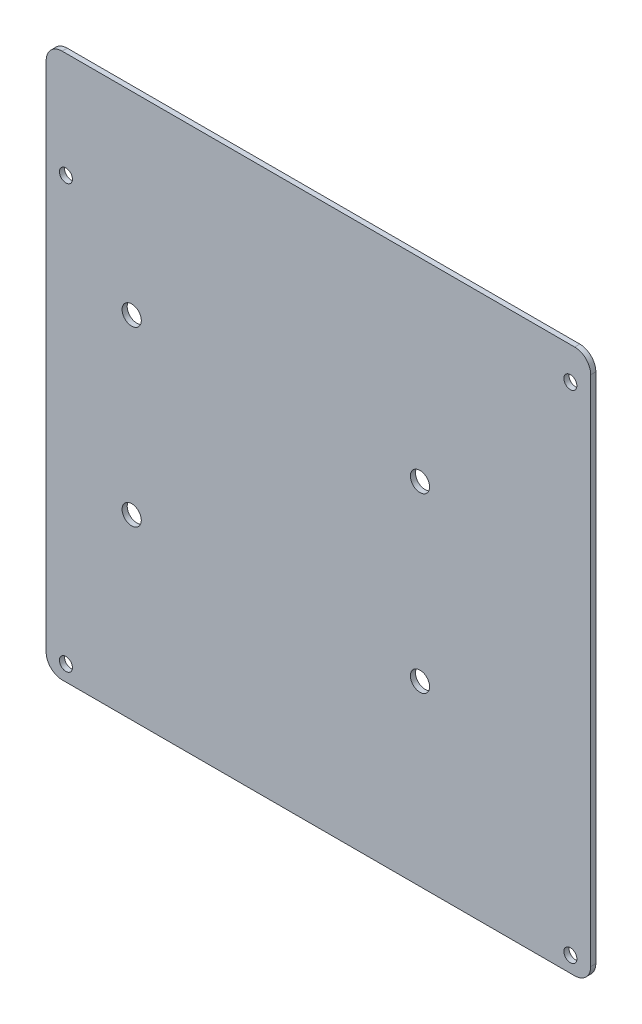
SolidWorks part; units mm, degrees
material "Epoxy, Unfilled"
ref_plane "Front Plane" through (0, 0, 0) normal (0, 0, 1) x (1, 0, 0)
ref_plane "Top Plane" through (0, 0, 0) normal (0, 1, 0) x (1, 0, 0)
ref_plane "Right Plane" through (0, 0, 0) normal (1, 0, 0) x (0, 0, -1)
sketch "Sketch1" plane through (0, 0, 0) normal (0, 0, 1) x (1, 0, 0)
  line L1 (85, -85) -> (-85, -85)
  line L2 (85, -85) -> (85, 85)
  line L3 (85, 85) -> (-85, 85)
  line L4 (-85, -85) -> (-85, 85)
  line L5 (85, -85) -> (-85, 85) construction
  line L6 (85, 85) -> (-85, -85) construction
  point P0 (0, 0)
  dimension "D1" = 170
  dimension "D2" = 170
extrude "Base" add sketch "Sketch1" along normal blind 1.6
fillet "Rounding corners" radius 5 4 edges at (-85, 85, 0.8) (85, 85, 0.8) (85, -85, 0.8) (-85, -85, 0.8)
sketch "Sketch2" plane through (0, 0, 1.6) normal (0, 0, 1) x (1, 0, 0)
  line L0 (85, -80) -> (85, 80) construction
  line L1 (80, 85) -> (-80, 85) construction
  circle A0 centre (-78.83, 51.98) radius 2.03
  circle A1 centre (78.65, 74.84) radius 2.03
  circle A2 centre (-78.83, -80.1) radius 2.03
  circle A3 centre (78.65, -80.1) radius 2.03
  point P12 (0, 0)
  dimension "D1" = 4.06
  dimension "D2" = 4.06
  dimension "D3" = 4.06
  dimension "D4" = 4.06
  dimension "D5" = 157.48
  dimension "D6" = 22.86
  dimension "D7" = 6.35
  dimension "D8" = 10.16
  dimension "D9" = 154.94
  dimension "D10" = 6.35
  dimension "D11" = 157.48
  dimension "D12" = 0
extrude "Mounting holes" cut sketch "Sketch2" against normal blind 1.6
sketch "Sketch4" plane through (0, 0, 1.6) normal (0, 0, 1) x (1, 0, 0)
  line L0 (-85, 80) -> (-85, -80) construction
  line L1 (-80, -85) -> (80, -85) construction
  circle A0 centre (-58.3, 24.5) radius 3
  circle A1 centre (31.7, 24.5) radius 3
  circle A2 centre (31.7, -29.5) radius 3
  circle A3 centre (-58.3, -29.5) radius 3
  point P12 (-51.1379, -48.724)
  dimension "D1" = 6
  dimension "D2" = 6
  dimension "D3" = 6
  dimension "D4" = 6
  dimension "D5" = 90
  dimension "D6" = 26.7
  dimension "D7" = 54
  dimension "D8" = 26.7
  dimension "D9" = 55.5
  dimension "D10" = 90
  dimension "D11" = 54
  dimension "D12" = 55.5
extrude "Cut-Extrude2" cut sketch "Sketch4" against normal blind 1.6
